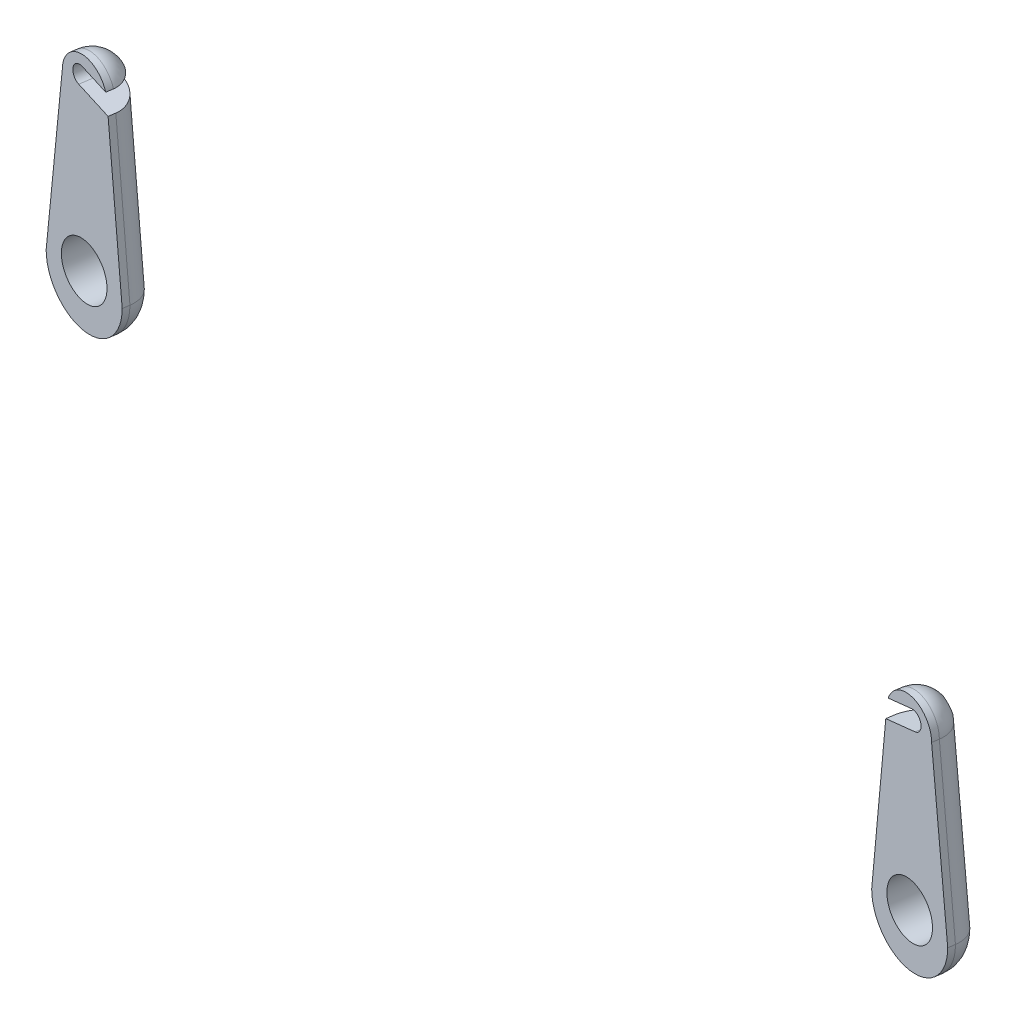
SolidWorks part; units mm, degrees
ref_plane "Front Plane" through (0, 0, 0) normal (0, 0, 1) x (1, 0, 0)
ref_plane "Top Plane" through (0, 0, 0) normal (0, 1, 0) x (1, 0, 0)
ref_plane "Right Plane" through (0, 0, 0) normal (1, 0, 0) x (0, 0, -1)
sketch "Sketch1" plane through (8.1146, -3.2834, -55.6766) normal (0.1442, 0, -0.9895) x (-0.9895, 0, -0.1442)
  line L0 (7.7839, 204.0844) -> (7.7839, 233.5484) construction
  line L1 (13.4843, 233.5484) -> (1.3539, 233.5484) construction
  line L2 (7.9153, 237.0844) -> (-3.6461, 237.0844) construction
  line L3 (-1.1061, 204.0844) -> (2.6653, 237.0844)
  line L4 (13.1653, 237.0844) -> (16.6739, 204.0844)
  line L6 (-3.6461, 243.0784) -> (-3.6461, 233.5484) construction
  line L8 (7.7839, 233.5484) -> (7.7839, 204.0844) construction
  line L9 (7.7839, 204.0844) -> (-3.6461, 204.0844) construction
  line L12 (7.7839, 204.0844) -> (7.7839, 233.5484) construction
  arc A1 (13.1653, 237.0844) -> (2.6653, 237.0844) centre (7.9153, 237.0844) ccw
  arc A2 (-1.1061, 204.0844) -> (16.6739, 204.0844) centre (7.7839, 204.0844) ccw
  dimension "D3" = 10.5
  dimension "D5" = 8.89
  dimension "D1" = 29.464
  dimension "D2" = 29.464
  dimension "D4" = 33
  dimension "D7" = 29.464
  dimension "D8" = 11.43
extrude "Base Extrude" add sketch "Sketch1" along normal blind 6.35
sketch "Sketch3" plane through (9.0304, -3.2834, -61.9602) normal (0.1442, 0, -0.9895) x (-0.9895, 0, -0.1442)
  line L0 (14.7164, 236.6382) -> (6.9306, 238.4771) construction
  line L1 (14.3026, 234.8864) -> (6.5168, 236.7253)
  line L2 (15.1301, 238.39) -> (7.3444, 240.2289)
  line L3 (9.1112, 236.4544) -> (9.1112, 237.9784) construction
  arc A0 (14.3026, 234.8864) -> (15.1301, 238.39) centre (14.7164, 236.6382) ccw
  arc A1 (7.3444, 240.2289) -> (6.5168, 236.7253) centre (6.9306, 238.4771) ccw
  circle A2 centre (9.1112, 237.9784) radius 1.524 construction
  point P3 (10.8235, 237.5577)
  dimension "D1" = 1.8
  dimension "D2" = 8
ref_plane "Rear Mirror Plane " through (-103.2134, 0, -15.0429) normal (0.9895, 0, 0.1442) x (0.1442, 0, -0.9895)
fillet "Fillet1" radius 5 4 edges at (1.1978, 239.051, -63.1018) (1.3279, 191.911, -63.0828) (-5.7332, 217.301, -64.112) (8.259, 217.301, -62.0727)
extrude "Cut-Extrude1" cut sketch "Sketch3" against normal up to surface (6.35 mm away) up to face at (0.3471, 216.391, -56.8087)
mirror "Mirror2" about plane through (-103.2134, 0, -15.0429) normal (0.9895, 0, 0.1442) of bodies 109
sketch "Sketch4" plane through (9.0304, 0, -61.9602) normal (0.1442, 0, -0.9895) x (-0.9895, 0, -0.1442)
  line L0 (2.7459, 202.201) -> (7.7839, 202.201) construction
  circle A0 centre (7.7839, 202.201) radius 5.0381 construction
  circle A1 centre (7.7839, 202.201) radius 5.334
  dimension "D1" = 10.668
extrude "Cut-Extrude2" cut sketch "Sketch4" against normal up to surface (6.35 mm away) up to face at (0.23, 224.1467, -56.8258)
mirror "Mirror3" about plane through (-103.2134, 0, -15.0429) normal (0.9895, 0, 0.1442) of "Cut-Extrude2"
